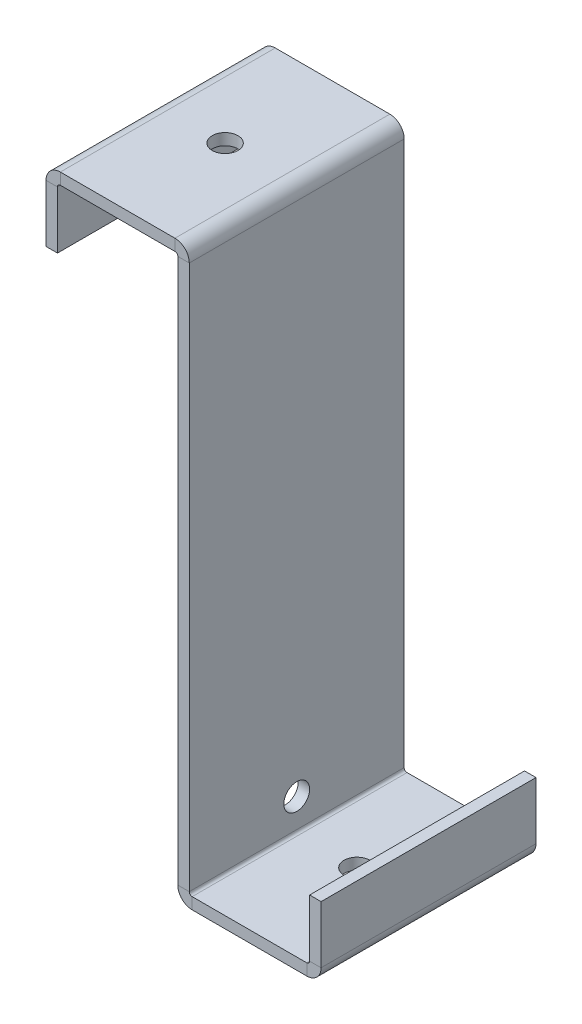
SolidWorks part; units mm, degrees
note: '?' marks a value the reader was unsure of. The reader was unsure of these and kept them because the rebuilt part matched: flange length of "Edge-Flange1", "Edge-Flange2".
ref_plane "Front Plane" through (0, 0, 0) normal (0, 0, 1) x (1, 0, 0)
ref_plane "Top Plane" through (0, 0, 0) normal (0, 1, 0) x (1, 0, 0)
ref_plane "Right Plane" through (0, 0, 0) normal (1, 0, 0) x (0, 0, -1)
sketch "BaseFlange" plane through (0, 0, 0) normal (1, 0, 0) x (0, 0, -1)
  line L1 (37.5, 200) -> (-37.5, 200)
  line L2 (37.5, 200) -> (37.5, 0)
  line L3 (37.5, 0) -> (-37.5, 0)
  line L4 (-37.5, 200) -> (-37.5, 0)
  line L5 (37.5, 200) -> (-37.5, 0) construction
  line L6 (37.5, 0) -> (-37.5, 200) construction
  point P0 (0, 100)
  dimension "Height" = 200
  dimension "D2" = 75
sheet metal parameters "Sheet-Metal1" thickness 4 parameters "D1"=1
base flange "Base-Flange1" sketch "BaseFlange" thickness 4 reverse thickness direction yes parameters "D1"=1
edge flange "Edge-Flange1" sketch "Sketch7" flange profiles "Sketch7", "Sketch8" flange angle 90 flange length 50 flange position material inside bend radius 1 thickness 4 parameters "D6"=10, "D8"=0.5
sketch "Sketch7" plane through (0, 200, 0) normal (0, -1, 0) x (0, 0, 1)
  line L1 (37.5, 0) -> (-37.5, 0) construction
  line L2 (-37.5, 0) -> (-37.5, 46)
  line L3 (-37.5, 46) -> (37.5, 46)
  line L4 (37.5, 46) -> (37.5, 0)
  line L5 (37.5, 0) -> (-37.5, 0)
sketch "Sketch8" plane through (4, 0, 0) normal (0, -1, 0) x (0, 0, -1)
  line L1 (-37.5, 0) -> (37.5, 0) construction
  line L2 (37.5, 0) -> (37.5, 46)
  line L3 (37.5, 46) -> (-37.5, 46)
  line L4 (-37.5, 46) -> (-37.5, 0)
  line L5 (-37.5, 0) -> (37.5, 0)
bend "EdgeBend1" bend radius 1 bend angle 90 parameters "D5"=1
bend "EdgeBend2" bend radius 1 bend angle 90 parameters "D5"=2
edge flange "Edge-Flange2" sketch "Sketch13" flange profiles "Sketch13", "Sketch14" flange angle 90 flange length 25 flange position material inside bend radius 1 thickness 4 parameters "D6"=10, "D8"=0.5
sketch "Sketch13" plane through (-46, 196, 0) normal (1, 0, 0) x (0, 0, 1)
  line L1 (37.5, 0) -> (-37.5, 0) construction
  line L2 (-37.5, 0) -> (-37.5, 21)
  line L3 (-37.5, 21) -> (37.5, 21)
  line L4 (37.5, 21) -> (37.5, 0)
  line L5 (37.5, 0) -> (-37.5, 0)
sketch "Sketch14" plane through (50, 4, 0) normal (1, 0, 0) x (0, 0, -1)
  line L1 (37.5, 0) -> (-37.5, 0) construction
  line L2 (37.5, 0) -> (37.5, 21)
  line L3 (37.5, 21) -> (-37.5, 21)
  line L4 (-37.5, 21) -> (-37.5, 0)
  line L5 (37.5, 0) -> (-37.5, 0)
bend "EdgeBend3" bend radius 1 bend angle 90 parameters "D5"=3
bend "EdgeBend4" bend radius 1 bend angle 90 parameters "D5"=4
sketch "Sketch15" plane through (0, 200, 0) normal (0, 1, 0) x (1, 0, 0)
  line L0 (-46, -37.5) -> (-46, 37.5) construction
  circle A0 centre (-21, 0) radius 4.5
  dimension "D1" = 25
  dimension "D2" = 9
extrude "Extrude1" cut sketch "Sketch15" against normal blind 4 normal cut yes
sketch "Sketch16" plane through (0, 0, 0) normal (0, -1, 0) x (1, 0, 0)
  line L3 (-1, 0) -> (108.3423, 0) construction
  line L4 (-1, 37.5) -> (-1, -37.5) construction
  line L5 (0, -37.5) -> (0, 37.5) construction
  line L6 (50, 37.5) -> (50, -37.5) construction
  circle A1 centre (25, 0) radius 4.5
  dimension "D3" = 9
  dimension "D1" = 25
  dimension "D2" = 25
extrude "Extrude2" cut sketch "Sketch16" against normal blind 4 normal cut yes
sketch "Sketch17" plane through (0, 0, 0) normal (-1, 0, 0) x (0, 0, 1)
  line L3 (37.5, 0) -> (-37.5, 0) construction
  circle A0 centre (0, 15) radius 4.5
  dimension "D1" = 9
  dimension "D4" = 15
extrude "Cut-Extrude1" cut sketch "Sketch17" against normal blind 4 normal cut yes
ref_axis "Axis1" through (-21, 196, 0) along (0, 1, 0)?
ref_axis "Axis2" through (4, 15, 0) along (-1, 0, 0)?
flat pattern "Flat-Pattern1" [suppressed]
sketch "Bend-Lines1" plane through (4, 0, 0) normal (1, 0, 0) x (0, 0, -1)
  line L0 (37.5, -139.2035) -> (-37.5, -139.2035) construction
  line L1 (-37.5, 139.2035) -> (37.5, 139.2035) construction
  line L2 (37.5, -96.4012) -> (-37.5, -96.4012) construction
  line L3 (-37.5, 96.4012) -> (37.5, 96.4012) construction
  line L4 (37.5, -139.2035) -> (-37.5, -139.2035) construction
  line L5 (-37.5, 139.2035) -> (37.5, 139.2035) construction
  line L6 (37.5, -96.4012) -> (-37.5, -96.4012) construction
  line L7 (-37.5, 96.4012) -> (37.5, 96.4012) construction
sketch3d "Bounding-Box1" [suppressed]
  line L0 (0, 260.6046, 0) -> (0, -60.6046, 0) construction
  line L1 (75, 260.6046, 0) -> (75, -60.6046, 0) construction
  line L2 (0, 260.6046, 0) -> (75, 260.6046, 0) construction
  line L3 (0, -60.6046, 0) -> (75, -60.6046, 0) construction
bend of the flat pattern "Flatten-<EdgeBend1>1"
bend of the flat pattern "Flatten-<EdgeBend2>1"
bend of the flat pattern "Flatten-<EdgeBend3>1"
bend of the flat pattern "Flatten-<EdgeBend4>1"
